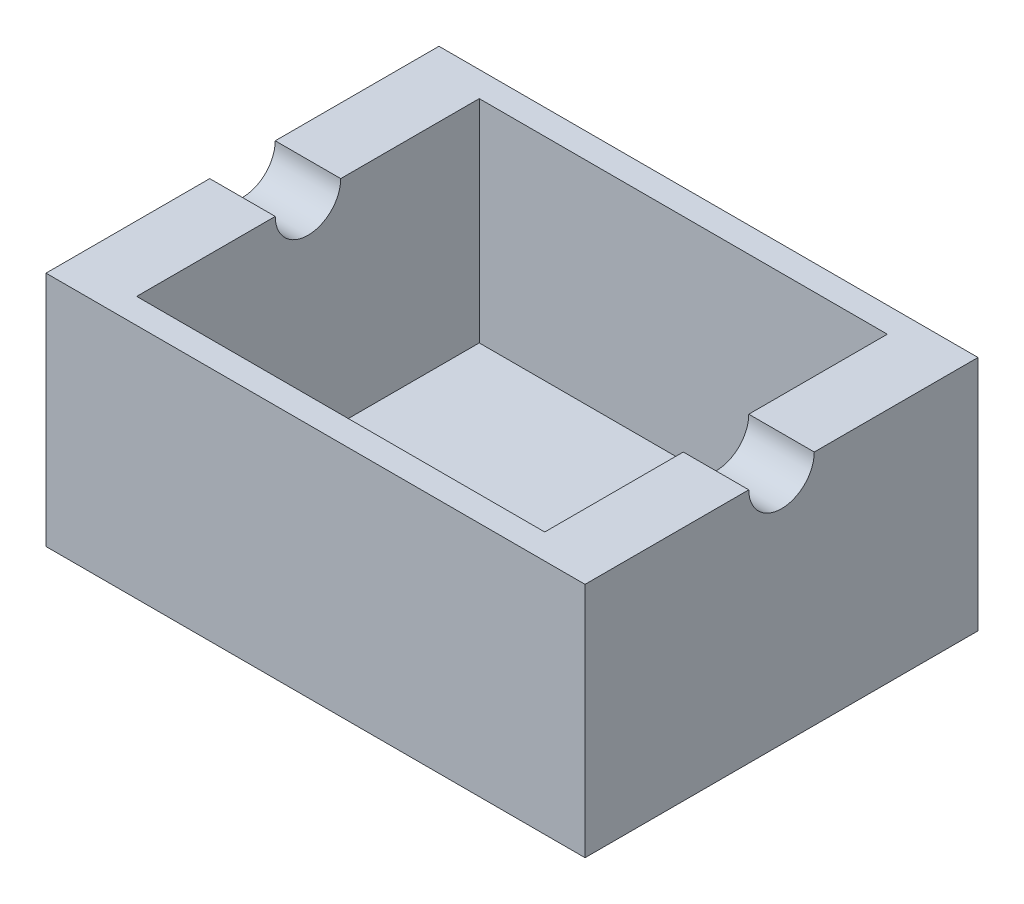
SolidWorks part; units mm, degrees
ref_plane "Alzado" through (0, 0, 0) normal (0, 0, 1) x (1, 0, 0)
ref_plane "Planta" through (0, 0, 0) normal (0, 1, 0) x (1, 0, 0)
ref_plane "Vista lateral" through (0, 0, 0) normal (1, 0, 0) x (0, 0, -1)
sketch "Croquis1" plane through (0, 0, 0) normal (0, 1, 0) x (1, 0, 0)
  line L1 (-16.2, -13.6) -> (16.2, -13.6)
  line L2 (-16.2, -13.6) -> (-16.2, 13.6)
  line L3 (-16.2, 13.6) -> (16.2, 13.6)
  line L4 (16.2, -13.6) -> (16.2, 13.6)
  line L5 (-16.2, -13.6) -> (16.2, 13.6) construction
  line L6 (-16.2, 13.6) -> (16.2, -13.6) construction
  line L7 (-21.4, -15.6) -> (21.4, -15.6)
  line L8 (-21.4, -15.6) -> (-21.4, 15.6)
  line L9 (-21.4, 15.6) -> (21.4, 15.6)
  line L10 (21.4, -15.6) -> (21.4, 15.6)
  line L11 (-21.4, -15.6) -> (21.4, 15.6) construction
  line L12 (-21.4, 15.6) -> (21.4, -15.6) construction
  point P0 (0, 0)
  point P6 (0, 0)
  dimension "D1" = 27.2
  dimension "D2" = 32.4
  dimension "D3" = 2
  dimension "D4" = 5.2
extrude "Saliente-Extruir1" add sketch "Croquis1" along normal blind 16.8
extrude "Saliente-Extruir2" add sketch "Croquis1<2>" against normal blind 2 contours L1 L4 L3 L2 | L7 L10 L9 L8 L4 L1 L2 L3 region at (0, 0, 0) region at (-20.8704, 0, 0)
sketch "Croquis1<2>" plane through (0, 0, 0) normal (0, 1, 0) x (1, 0, 0) same geometry as "Croquis1"
ref_plane "Plano1" through (21.4, 0, 0) normal (1, 0, 0) x (0, 0, -1)
sketch "Croquis2" plane through (21.4, 0, 0) normal (1, 0, 0) x (0, 0, -1)
  line L0 (-15.6, 16.8) -> (15.6, 16.8) construction
  line L1 (-2.6, 16.8) -> (2.6, 16.8)
  arc A0 (2.6, 16.8) -> (-2.6, 16.8) centre (0, 16.8) cw
  dimension "D1" = 2.6
extrude "Cortar-Extruir1" cut sketch "Croquis2" against normal up to surface (42.8 mm away) up to face at (-21.4, 7.4, 0)
